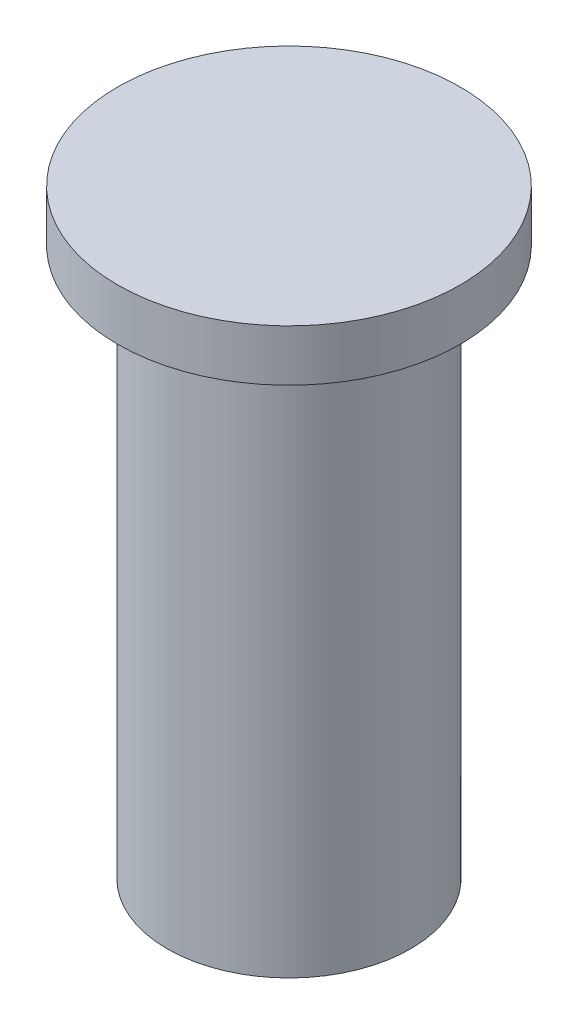
SolidWorks part; units mm, degrees
ref_plane "Front Plane" through (0, 0, 0) normal (0, 0, 1) x (1, 0, 0)
ref_plane "Top Plane" through (0, 0, 0) normal (0, 1, 0) x (1, 0, 0)
ref_plane "Right Plane" through (0, 0, 0) normal (1, 0, 0) x (0, 0, -1)
sketch "Sketch1" plane through (0, 0, 0) normal (0, 1, 0) x (1, 0, 0)
  circle A0 centre (0, 0) radius 3.55
extrude "Boss-Extrude1" add sketch "Sketch1" along normal blind 16
sketch "Sketch2" plane through (0, 16, 0) normal (0, 1, 0) x (1, 0, 0)
  circle A0 centre (0, 0) radius 5
extrude "Boss-Extrude2" add sketch "Sketch2" along normal blind 1.5
